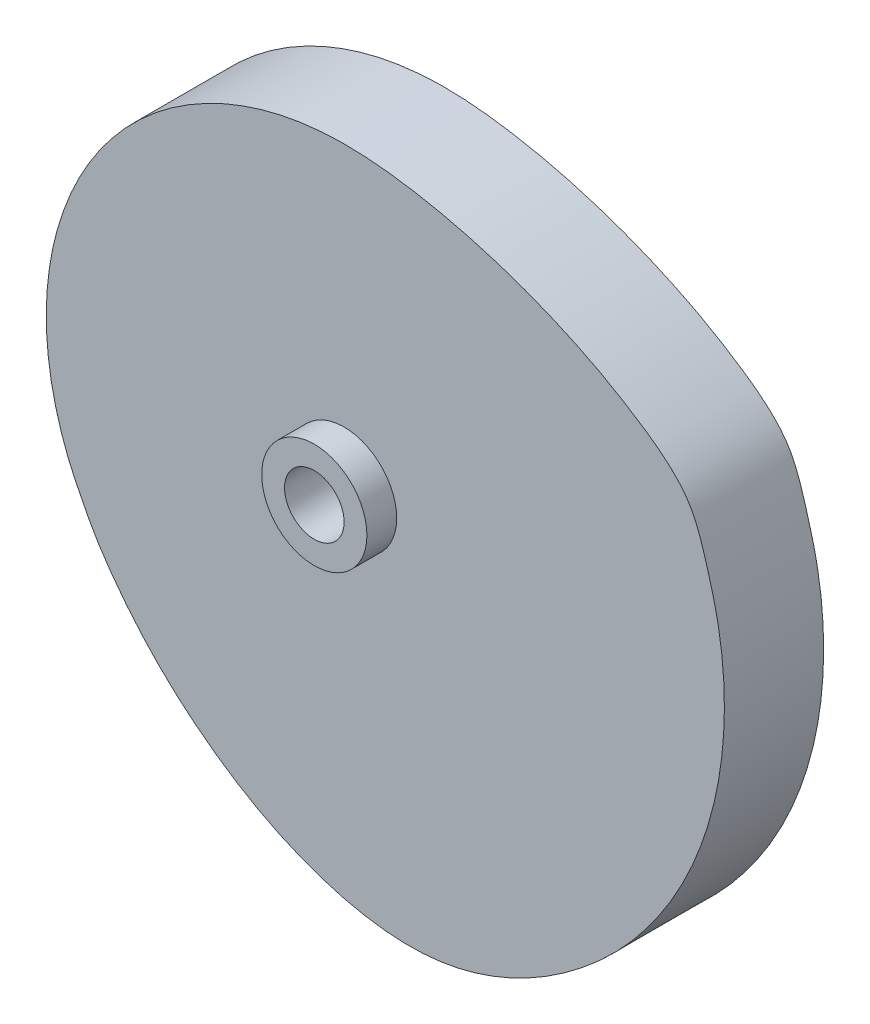
SolidWorks part; units mm, degrees
ref_plane "Front Plane" through (0, 0, 0) normal (0, 0, 1) x (1, 0, 0)
ref_plane "Top Plane" through (0, 0, 0) normal (0, 1, 0) x (1, 0, 0)
ref_plane "Right Plane" through (0, 0, 0) normal (1, 0, 0) x (0, 0, -1)
sketch "Sketch2" plane through (0, 0, 0) normal (0, 0, 1) x (1, 0, 0)
  line L0 (0, 0) -> (511.6441, 0) construction
  line L1 (0, 0) -> (0, 441.4409) construction
  line L2 (0, 0) -> (255.6687, 230.8803) construction
  line L3 (0, 0) -> (84.1122, 291.1671) construction
  line L4 (0, 0) -> (113.0497, 284.8481) construction
  line L5 (0, 0) -> (296.0137, 206.8761) construction
  line L6 (0, 0) -> (335.5878, 175.5142) construction
  line L7 (0, 0) -> (343.881, 165.6782) construction
  line L8 (0, 0) -> (376.7762, 69.4583) construction
  line L9 (0, 0) -> (374.118, -82.5861) construction
  line L10 (0, 0) -> (312.52, -221.6198) construction
  line L11 (0, 0) -> (202.7, -325.08) construction
  line L12 (0, 0) -> (101.49, -364.25) construction
  line L13 (0, 0) -> (-31.7, -348.71) construction
  line L14 (0, 0) -> (-138.14, -290.4) construction
  line L15 (0, 0) -> (-204.6, -229.15) construction
  line L16 (0, 0) -> (230.57, 243.43) construction
  line L17 (0, 0) -> (137.1053, 278.4556) construction
  line L18 (0, 0) -> (78.81, -366.64) construction
  line L19 (369.52, -101.16) -> (0, 0) construction
  line L20 (0, 0) -> (1379.3121, 448.1657) construction
  line L21 (0, 0) -> (898.1591, -1236.2099) construction
  line L22 (0, 0) -> (-1251.1269, -406.5158) construction
  arc A1 (225.204, -309.9668) -> (364.3878, 118.3968) centre (0, 0) ccw
  arc A2 (-285.317, -92.7051) -> (-263.7937, -142.8737) centre (0, 0) ccw
  spline S0 degree 3 poles (84.1122, 291.1671) (101.9651, 287.7344) (151.9879, 275.664) (209.23, 254.278) (261.4517, 228.3159) (297.2459, 206.8074) (341.8295, 175.2111) (361.0009, 140.2907) (364.3878, 118.3968) knots 0 0 0 0 0.158355 0.448315 0.529836 0.666217 0.812906 1 1 1 1
  spline S1 degree 3 poles (225.204, -309.9668) (188.8899, -336.409) (139.0063, -360.7033) (49.2328, -370.135) (-67.7239, -347.6278) (-157.4072, -281.4619) (-204.6, -229.15) knots 0 0 0 0 0.281316 0.328617 0.560822 1 1 1 1
  spline S2 degree 2 poles (-204.6, -229.15) (-258.0754, -169.4911) (-285.317, -92.7051) knots 0 0 0 1 1 1
  spline S4 degree 3 poles (0, 300) (38.2386, 299.5339) (84.321, 292.66) (161.2826, 272.1942) (209.2358, 254.2799) (261.4451, 228.3134) (297.293, 206.8256) (327.5045, 185.2228) (352.627, 156.0419) (364.7664, 118.5845) (378.2353, 68.9469) (385.6961, 1.2639) (380.7252, -56.5722) (360.5409, -138.1098) (330.7399, -201.1036) (276.3732, -267.8227) (238.1712, -301.6162) (180.4515, -340.5127) (129.9992, -361.6533) (49.2377, -370.1312) (-37.2377, -353.5352) (-132.304, -299.8113) (-210.4274, -227.8396) (-248.0693, -174.2267) (-263.7937, -142.8737) knots 0 0 0 0 0.076331 0.092968 0.159685 0.178442 0.209822 0.243574 0.252174 0.286623 0.320367 0.355845 0.422477 0.435267 0.524345 0.558557 0.607642 0.625761 0.698303 0.713547 0.788381 0.869505 0.929917 1 1 1 1
  spline S5 degree 3 poles (-55.7759, 296.6307) (10.2713, 302.3906) (66.2766, 295.2823) (111.5652, 285.4231) (161.2848, 272.1844) (209.2356, 254.2808) (261.4452, 228.3132) (297.2929, 206.8257) (327.5046, 185.2228) (352.6267, 156.0418) (364.7708, 118.5855) (379.6651, 63.6072) (385.6091, -4.4947) (379.4034, -61.9331) (365.3959, -118.4565) (347.2856, -166.4803) (315.5707, -219.6547) (276.3725, -267.8478) (238.1712, -301.6138) (180.4514, -340.5145) (129.9989, -361.6533) (49.2382, -370.131) (-37.25, -353.5415) (-132.2613, -299.7893) (-195.5042, -241.7175) (-232.0918, -195.9381) (-251.6767, -166.8316) (-264.9473, -140.5754) (-276.1798, -118.4947) (-289.3825, -82.8812) (-299.3887, -37.6183) (-301.0255, 17.3435) (-290.3898, 90.7643) (-252.4635, 173.7441) (-183.7262, 242.287) (-116.0547, 279.3258) (-55.7759, 296.6307) (10.2713, 302.3906) (66.2766, 295.2823) knots -0.088367 -0.053546 -0.025458 0 0.039987 0.053991 0.065759 0.11295 0.126217 0.148413 0.172287 0.17837 0.202736 0.226604 0.259582 0.29886 0.307907 0.342171 0.371156 0.395355 0.430074 0.442891 0.494201 0.504984 0.557916 0.615297 0.658029 0.678834 0.698359 0.707629 0.720548 0.733466 0.76141 0.78586 0.811058 0.866205 0.911633 0.946454 0.974542 1 1.039987 1.053991 1.065759 only from (0, 300) to (0, 300)
  point P3 (255.6687, 230.8803)
  point P6 (113.0497, 284.8481)
  point P8 (84.1122, 291.1671)
  point P9 (296.0137, 206.8761)
  point P10 (335.5878, 175.5142)
  point P11 (343.881, 165.6782)
  point P15 (376.7762, 69.4583)
  point P18 (374.118, -82.5861)
  point P20 (312.52, -221.6198)
  point P22 (202.7, -325.08)
  point P23 (101.49, -364.25)
  point P26 (-31.7, -348.71)
  point P28 (-138.14, -290.4)
  point P30 (-204.6, -229.15)
  point P32 (230.57, 243.43)
  point P34 (137.1053, 278.4556)
  point P36 (78.81, -366.64)
  point P38 (202.7, -325.08)
  point P39 (369.52, -101.16)
  point P46 (-254.71, -160.25)
  point P48 (-175.3335, 243.43)
  point P61 (-285.317, -92.7051)
  point P62 (-232.1662, -194.8493)
  point P64 (0, 300)
  point P67 (-110.7407, 278.8127)
  point P68 (-243.2997, 175.5142)
  point P69 (-291.8485, 69.4583)
  point P70 (-299.5337, 16.7209)
  point P71 (-297.9551, -34.9683)
  point P72 (-53.6284, 295.1677)
  point P73 (280.2028, -261.3095)
  point P74 (343.881, -168.9441)
  point P75 (382.775, 16.7209)
  dimension "D40" = 766.28
  dimension "D2" = 230.8803
  dimension "D3" = 255.6687
  dimension "D4" = 84.1122
  dimension "D5" = 113.0497
  dimension "D6" = 291.1671
  dimension "D7" = 296.0137
  dimension "D8" = 206.8761
  dimension "D9" = 335.5878
  dimension "D10" = 175.5142
  dimension "D11" = 165.6782
  dimension "D12" = 343.881
  dimension "D13" = 69.4583
  dimension "D14" = 376.7762
  dimension "D15" = 82.5861
  dimension "D16" = 374.118
  dimension "D17" = 221.6198
  dimension "D18" = 312.52
  dimension "D19" = 325.08
  dimension "D20" = 202.7
  dimension "D21" = 364.25
  dimension "D22" = 101.49
  dimension "D23" = 348.71
  dimension "D24" = 31.7
  dimension "D25" = 290.4
  dimension "D26" = 138.14
  dimension "D27" = 204.6
  dimension "D28" = 229.15
  dimension "D29" = 230.57
  dimension "D30" = 243.43
  dimension "D31" = 137.1053
  dimension "D32" = 278.4556
  dimension "D33" = 78.81
  dimension "D34" = 366.64
  dimension "D35" = 325.08
  dimension "D36" = 101.16
  dimension "D37" = 369.52
  dimension "D38" = 72
  dimension "D39" = 72
  dimension "D41" = 252
  dimension "D42" = 254.71
  dimension "D43" = 160.25
extrude "Boss-Extrude2" add sketch "Sketch2" along normal mid plane 100 contours S5
sketch "Sketch4" plane through (0, 0, 0) normal (0, 0, 1) x (1, 0, 0)
  circle A0 centre (0, 0) radius 30
  dimension "D1" = 60
extrude "Cut-Extrude1" cut sketch "Sketch4" against normal mid plane 240
sketch "Sketch5" plane through (0, 0, 50) normal (0, 0, 1) x (1, 0, 0)
  circle A0 centre (0, 0) radius 53
  circle A1 centre (0, 0) radius 30
  dimension "D1" = 106
extrude "Boss-Extrude5" add sketch "Sketch5" along normal blind 30
mirror "Mirror1" about plane through (0, 0, 0) normal (0, 0, 1) of "Boss-Extrude5"
ref_axis "Axis1" through (0, 0, 80) along (0, 0, -1)
